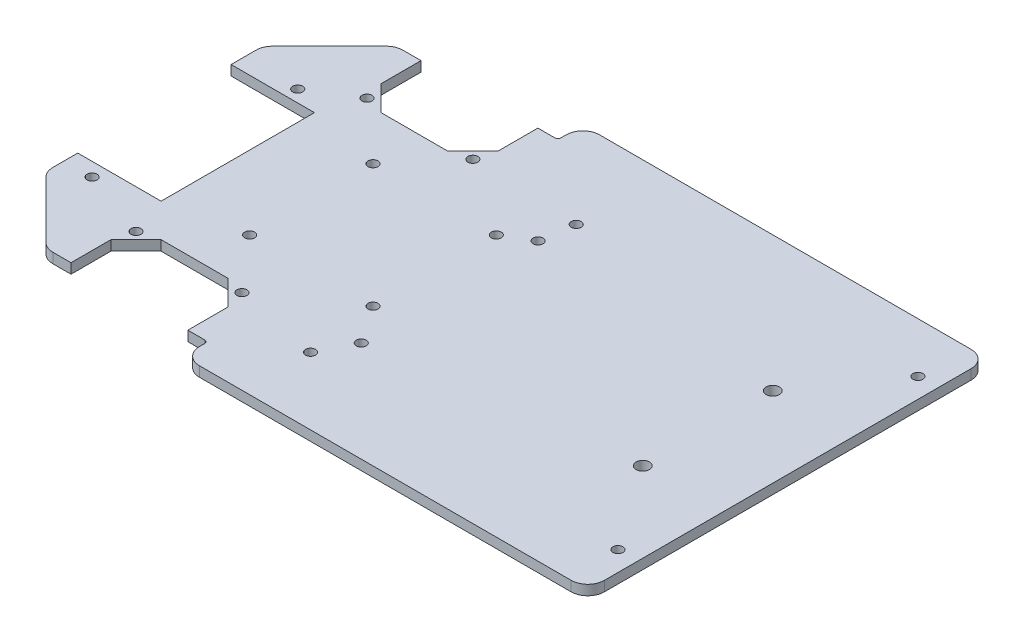
SolidWorks part; units mm, degrees
ref_plane "Front Plane" through (0, 0, 0) normal (0, 0, 1) x (1, 0, 0)
ref_plane "Top Plane" through (0, 0, 0) normal (0, 1, 0) x (1, 0, 0)
ref_plane "Right Plane" through (0, 0, 0) normal (1, 0, 0) x (0, 0, -1)
sketch "Sketch1" plane through (0, 0, 0) normal (0, 1, 0) x (1, 0, 0)
  line L0 (190, 0) -> (0, 0) construction
  line L1 (0, -60) -> (190, -60)
  line L2 (0, -60) -> (0, 60)
  line L3 (0, 60) -> (190, 60)
  line L4 (190, -60) -> (190, 60)
  line L5 (0, -32.5266) -> (27.4734, -60)
  line L6 (25, 23) -> (0, 23) construction
  line L7 (25, 23) -> (25, -23) construction
  line L8 (25, -23) -> (0, -23) construction
  line L9 (0, 23) -> (0, -23)
  line L10 (25, 23) -> (0, -23) construction
  line L11 (25, -23) -> (0, 23) construction
  line L12 (19.9734, -52.5) -> (27.4734, -52.5) construction
  line L13 (68.5266, -52.5) -> (68.5266, -60) construction
  line L14 (35, -33) -> (27.4734, -40.5266) construction
  line L15 (27.4734, -52.5) -> (27.4734, -40.5266) construction
  line L16 (27.4734, -40.5266) -> (27.4734, -52.5) construction
  line L17 (0, 32.5266) -> (27.4734, 60)
  line L18 (35, -33) -> (55, -33) construction
  line L19 (55, -33) -> (62.5266, -40.5266) construction
  line L20 (62.5266, -52.5) -> (68.5266, -52.5) construction
  line L21 (47.5, -37) -> (42.5, -37) construction
  line L22 (45, -37) -> (45, -33) construction
  line L23 (45, -56.5) -> (45, -52.5) construction
  line L24 (39.4, -56.5) -> (50.6, -56.5) construction
  line L25 (27.4734, -52.5) -> (62.5266, -52.5) construction
  line L27 (62.5266, -40.5266) -> (62.5266, -52.5) construction
  point P7 (0, 0)
  point P8 (12.5, 0)
  dimension "D1" = 120
  dimension "D2" = 190
  dimension "D3" = 25
  dimension "D4" = 23
  dimension "D5" = 10
  dimension "D6" = 20
  dimension "D7" = 45
  dimension "D8" = 45
  dimension "D9" = 45
  dimension "D10" = 7.5
  dimension "D11" = 6
extrude "Boss-Extrude1" add sketch "Sketch1" along normal blind 3 contours L7 L8 L2 L1 L4 L3 L6 region at (97.9391, 0, 0)
sketch "Sketch4" plane through (0, 0, 0) normal (0, 1, 0) x (1, 0, 0)
  line L0 (68.5266, -60) -> (68.5266, -52.5)
  line L1 (68.5266, -52.5) -> (62.5266, -52.5)
  line L2 (62.5266, -52.5) -> (62.5266, -40.5266)
  line L3 (62.5266, -40.5266) -> (55, -33)
  line L4 (55, -33) -> (35, -33)
  line L5 (35, -33) -> (27.4734, -40.5266)
  line L6 (27.4734, -40.5266) -> (27.4734, -52.5)
  line L7 (27.4734, -52.5) -> (19.9734, -52.5)
  line L8 (19.9734, -52.5) -> (27.4734, -60)
  line L9 (27.4734, -60) -> (68.5266, -60)
  line L10 (0, 0) -> (190, 0) construction
  line L11 (190, -60) -> (190, 60) construction
  line L12 (27.4734, 60) -> (68.5266, 60)
  line L13 (19.9734, 52.5) -> (27.4734, 60)
  line L14 (27.4734, 52.5) -> (19.9734, 52.5)
  line L15 (27.4734, 40.5266) -> (27.4734, 52.5)
  line L16 (35, 33) -> (27.4734, 40.5266)
  line L17 (55, 33) -> (35, 33)
  line L18 (62.5266, 40.5266) -> (55, 33)
  line L19 (62.5266, 52.5) -> (62.5266, 40.5266)
  line L20 (68.5266, 52.5) -> (62.5266, 52.5)
  line L21 (68.5266, 60) -> (68.5266, 52.5)
  line L23 (25, 23) -> (0, 23)
  line L24 (25, 23) -> (25, -23)
  line L25 (25, -23) -> (0, -23)
  line L26 (0, 23) -> (0, -23)
extrude "Cut-Extrude1" cut sketch "Sketch4" along normal up to surface (3 mm away) up to face at (72.4911, 3, 0)
fillet "Fillet1" radius 5 8 edges at (19.9734, 1.5, -52.5) (0, 1.5, -32.5266) (68.5266, 1.5, -60) (190, 1.5, -60) (190, 1.5, 60) (0, 1.5, 32.5266) (19.9734, 1.5, 52.5) (68.5266, 1.5, 60)
fillet "Fillet2" radius 1 2 edges at (68.5266, 1.5, -52.5) (68.5266, 1.5, 52.5)
sketch "Sketch5" plane through (0, 0, 0) normal (0, 1, 0) x (1, 0, 0)
  circle A0 centre (47.0626, -18.5) radius 1.5 construction
  circle A1 centre (47.0626, -18.5) radius 1.5
  circle A2 centre (84.0626, -18.5) radius 1.5 construction
  circle A3 centre (84.0626, -18.5) radius 1.5
  circle A4 centre (84.0626, 18.5) radius 1.5 construction
  circle A5 centre (84.0626, 18.5) radius 1.5
  circle A6 centre (47.0626, 18.5) radius 1.5 construction
  circle A7 centre (47.0626, 18.5) radius 1.5
  circle A8 centre (91.88, 23.2195) radius 1.5 construction
  circle A9 centre (91.88, 23.2195) radius 1.5
  circle A10 centre (93.3054, 33.2195) radius 1.5 construction
  circle A11 centre (93.3054, 33.2195) radius 1.5
  circle A12 centre (29.1154, 34.642) radius 1.5 construction
  circle A13 centre (60.8846, 34.642) radius 1.5 construction
  circle A14 centre (8.3674, -27.0854) radius 1.5 construction
  circle A15 centre (16.3794, 26.6064) radius 1.5 construction
  circle A16 centre (91.88, -29.8422) radius 1.5 construction
  circle A17 centre (86.6598, -39.8422) radius 1.5 construction
  circle A18 centre (29.1154, 34.642) radius 1.5
  circle A19 centre (60.8846, 34.642) radius 1.5
  circle A20 centre (8.3674, -27.0854) radius 1.5
  circle A21 centre (16.3794, 26.6064) radius 1.5
  circle A22 centre (91.88, -29.8422) radius 1.5
  circle A23 centre (86.6598, -39.8422) radius 1.5
  circle A24 centre (184.0458, -45) radius 1.5 construction
  circle A25 centre (184.0458, 45) radius 1.5 construction
  circle A26 centre (184.0458, -45) radius 1.5
  circle A27 centre (184.0458, 45) radius 1.5
  circle A28 centre (166, -19.5) radius 2 construction
  circle A29 centre (166, 19.5) radius 2 construction
  circle A30 centre (166, -19.5) radius 2
  circle A31 centre (166, 19.5) radius 2
  circle A32 centre (29.1154, -34.642) radius 1.5 construction
  circle A33 centre (60.8846, -34.642) radius 1.5 construction
  circle A34 centre (29.1154, -34.642) radius 1.5
  circle A35 centre (60.8846, -34.642) radius 1.5
extrude "Cut-Extrude2" cut sketch "Sketch5" along normal up to surface (3 mm away) up to face at (54.9908, 3, 0)
